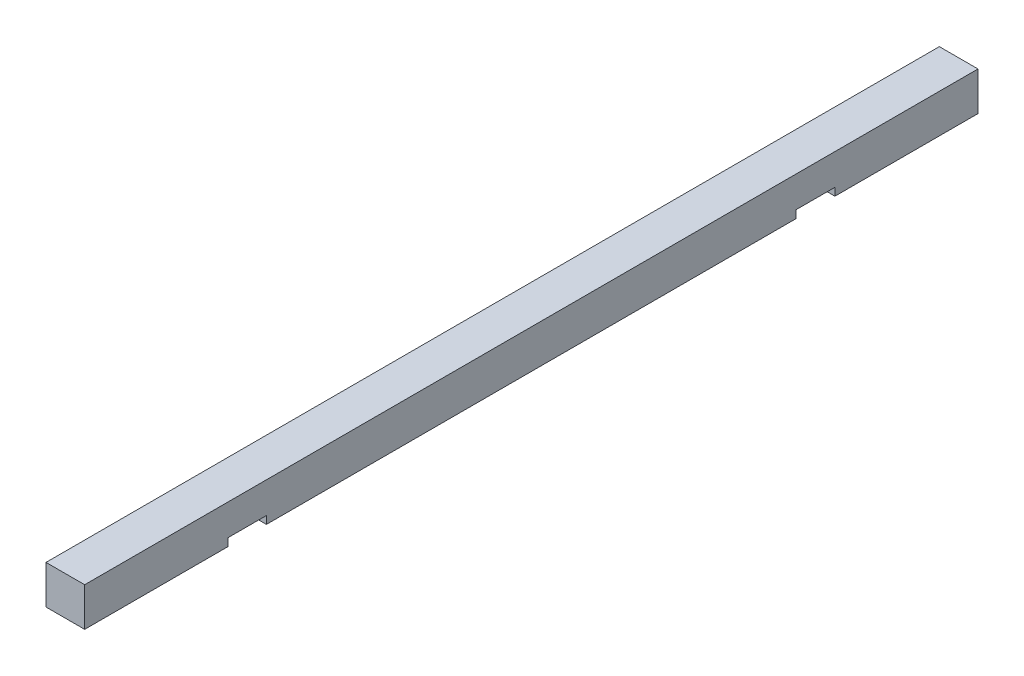
SolidWorks part; units mm, degrees
ref_plane "Plan de face" through (0, 0, 0) normal (0, 0, 1) x (1, 0, 0)
ref_plane "Plan de dessus" through (0, 0, 0) normal (0, 1, 0) x (1, 0, 0)
ref_plane "Plan de droite" through (0, 0, 0) normal (1, 0, 0) x (0, 0, -1)
sketch "Esquisse1" plane through (0, 0, 0) normal (0, 0, 1) x (1, 0, 0)
  line L1 (0, 0) -> (10, 0)
  line L2 (0, 0) -> (0, 10)
  line L3 (0, 10) -> (10, 10)
  line L4 (10, 0) -> (10, 10)
  dimension "D1" = 10
  dimension "D2" = 10
extrude "Boss.-Extru.1" add sketch "Esquisse1" along normal blind 231
sketch "Esquisse2" plane through (0, 0, 0) normal (0, -1, 0) x (1, 0, 0)
  line L0 (0, 231) -> (0, 0) construction
  line L1 (0, 184) -> (10, 184)
  line L2 (0, 184) -> (0, 194)
  line L3 (0, 194) -> (10, 194)
  line L4 (10, 184) -> (10, 194)
  line L5 (10, 231) -> (10, 0) construction
  line L6 (0, 231) -> (10, 231) construction
  point P10 (5, 231)
  dimension "D1" = 10
  dimension "D2" = 37
extrude "Enlèv. mat.-Extru.1" cut sketch "Esquisse2" against normal blind 2
sketch "Esquisse3" plane through (0, 0, 0) normal (0, -1, 0) x (1, 0, 0)
  line L0 (0, 184) -> (0, 0) construction
  line L1 (0, 37) -> (10, 37)
  line L2 (0, 37) -> (0, 47)
  line L3 (0, 47) -> (10, 47)
  line L4 (10, 37) -> (10, 47)
  line L5 (10, 184) -> (10, 0) construction
  line L6 (0, 0) -> (10, 0) construction
  point P10 (5, 0)
  dimension "D1" = 10
  dimension "D2" = 37
extrude "Enlèv. mat.-Extru.2" cut sketch "Esquisse3" against normal blind 2
